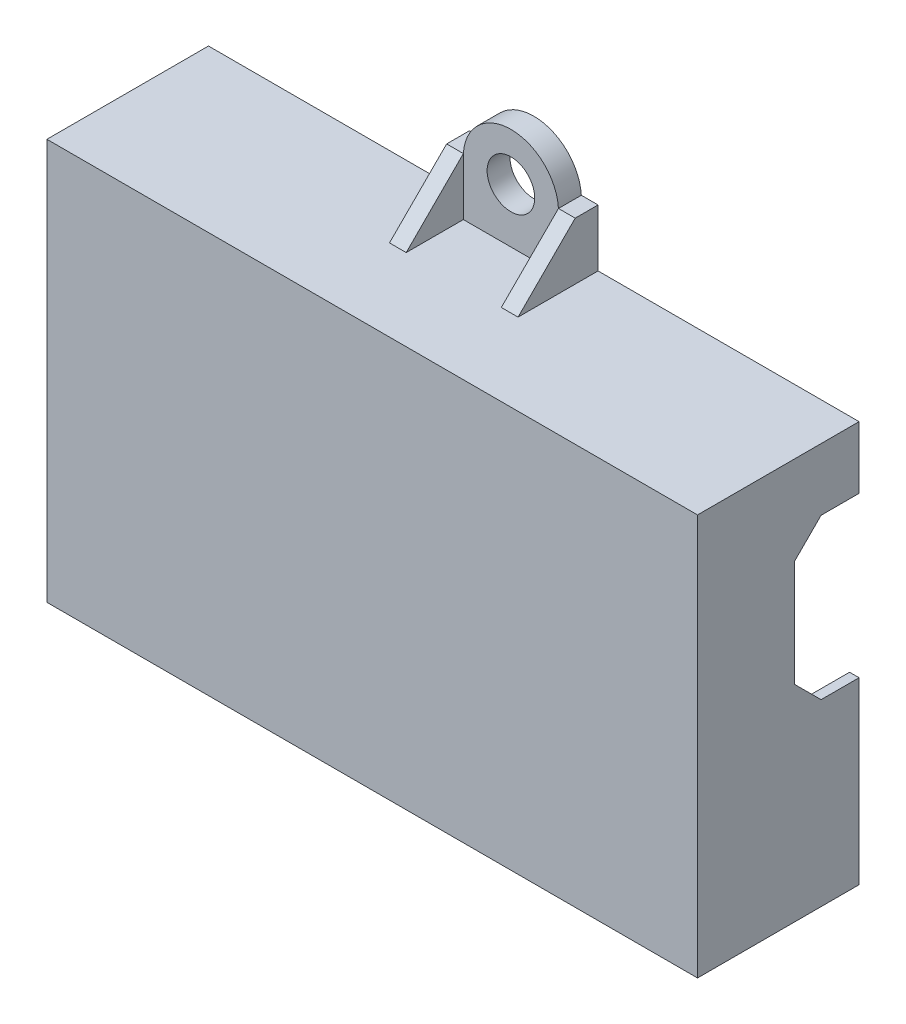
SolidWorks part; units mm, degrees
ref_plane "Front Plane" through (0, 0, 0) normal (0, 0, 1) x (1, 0, 0)
ref_plane "Top Plane" through (0, 0, 0) normal (0, 1, 0) x (1, 0, 0)
ref_plane "Right Plane" through (0, 0, 0) normal (1, 0, 0) x (0, 0, -1)
sketch "Sketch1" plane through (0, 0, 0) normal (0, 0, 1) x (1, 0, 0)
  line L0 (-16.375, 9.825) -> (16.375, -9.825) construction
  line L1 (-16.375, -9.825) -> (-16.575, -9.825) construction
  line L2 (16.575, 10.025) -> (-16.575, 10.025)
  line L3 (16.575, 10.025) -> (16.575, -10.025)
  line L4 (-16.375, 9.825) -> (-16.375, -9.825)
  line L5 (-16.375, -9.825) -> (16.375, -9.825)
  line L6 (16.375, -9.825) -> (16.375, 9.825)
  line L7 (16.375, 9.825) -> (-16.375, 9.825)
  line L8 (-16.375, 9.825) -> (-16.375, -9.825)
  line L9 (-16.375, -9.825) -> (16.375, -9.825)
  line L10 (16.375, -9.825) -> (16.375, 9.825)
  line L11 (16.375, 9.825) -> (-16.375, 9.825)
  line L12 (16.575, -10.025) -> (-16.575, -10.025)
  line L13 (-16.575, 10.025) -> (-16.575, -10.025)
  line L14 (16.575, 10.025) -> (-16.575, -10.025) construction
  line L15 (-13.9701, -11.875) -> (-3.4641, -11.875)
  line L18 (3.4641, -11.875) -> (13.9701, -11.875)
  line L19 (14.8161, -12.3418) -> (24.6724, -27.981)
  line L20 (31.4404, -23.7156) -> (19.404, -4.6171)
  line L21 (19.25, -4.084) -> (19.25, 4.084)
  line L22 (19.404, 4.6171) -> (31.4404, 23.7156)
  line L23 (24.6724, 27.981) -> (14.8161, 12.3418)
  line L24 (13.9701, 11.875) -> (3.4641, 11.875)
  line L25 (-3.4641, 11.875) -> (-13.9701, 11.875)
  line L26 (-14.8161, 12.3418) -> (-24.6724, 27.981)
  line L27 (-31.4404, 23.7156) -> (-19.404, 4.6171)
  line L28 (-19.25, 4.084) -> (-19.25, 3.4641)
  line L29 (-19.25, -3.4641) -> (-19.25, -4.084)
  line L30 (-19.404, -4.6171) -> (-31.4404, -23.7156)
  line L31 (-24.6724, -27.981) -> (-14.8161, -12.3418)
  line L32 (-13.9701, -11.875) -> (-3.4641, -11.875)
  line L33 (3.4641, -11.875) -> (13.9701, -11.875)
  line L34 (14.8161, -12.3418) -> (24.6724, -27.981)
  line L35 (31.4404, -23.7156) -> (19.404, -4.6171)
  line L36 (19.25, -4.084) -> (19.25, 4.084)
  line L37 (19.404, 4.6171) -> (31.4404, 23.7156)
  line L38 (24.6724, 27.981) -> (14.8161, 12.3418)
  line L39 (13.9701, 11.875) -> (3.4641, 11.875)
  line L40 (-3.4641, 11.875) -> (-13.9701, 11.875)
  line L41 (-14.8161, 12.3418) -> (-24.6724, 27.981)
  line L42 (-31.4404, 23.7156) -> (-19.404, 4.6171)
  line L43 (-19.25, 4.084) -> (-19.25, 3.4641)
  line L44 (-19.25, -3.4641) -> (-19.25, -4.084)
  line L45 (-19.404, -4.6171) -> (-31.4404, -23.7156)
  line L46 (-24.6724, -27.981) -> (-14.8161, -12.3418)
  line L47 (16.575, -10.025) -> (-16.575, 10.025) construction
  line L48 (-16.375, -9.825) -> (-16.375, -10.025) construction
  line L49 (-16.575, -10.025) -> (-17.075, -10.025) construction
  line L50 (17.075, 10.525) -> (-17.075, 10.525)
  line L51 (17.075, 10.525) -> (17.075, -10.525)
  line L52 (17.075, -10.525) -> (-17.075, -10.525)
  line L53 (-17.075, 10.525) -> (-17.075, -10.525)
  line L54 (17.075, 10.525) -> (-17.075, -10.525) construction
  line L55 (17.075, -10.525) -> (-17.075, 10.525) construction
  line L56 (-16.575, -10.025) -> (-16.575, -10.525) construction
  line L57 (-20.3929, -2.4744) -> (-17.075, -2.4744)
  line L58 (-20.3929, 2.4744) -> (-17.075, 2.4744)
  line L59 (-2.4744, -13.0179) -> (-2.4744, -10.525)
  line L60 (2.4744, -13.0179) -> (2.4744, -10.525)
  line L61 (-2.4744, 13.0179) -> (-2.4744, 10.525)
  line L62 (2.4744, 13.0179) -> (2.4744, 10.525)
  circle A0 centre (0, -13.375) radius 1.25
  circle A1 centre (-20.75, 0) radius 1.25
  circle A2 centre (0, 13.375) radius 1.25
  arc A32 (-2.4744, -13.0179) -> (-3.4641, -11.875) centre (-3.4641, -12.875) ccw
  arc A33 (-2.4744, -13.0179) -> (2.4744, -13.0179) centre (0, -13.375) ccw
  arc A34 (3.4641, -11.875) -> (2.4744, -13.0179) centre (3.4641, -12.875) ccw
  arc A35 (14.8161, -12.3418) -> (13.9701, -11.875) centre (13.9701, -12.875) ccw
  arc A36 (24.7505, -28.8963) -> (24.6724, -27.981) centre (23.8264, -28.5142) ccw
  arc A37 (24.7505, -28.8963) -> (32.2325, -24.1809) centre (31.8198, -31.8198) ccw
  arc A38 (31.4404, -23.7156) -> (32.2325, -24.1809) centre (32.2864, -23.1824) ccw
  arc A39 (19.25, -4.084) -> (19.404, -4.6171) centre (20.25, -4.084) ccw
  arc A40 (19.404, 4.6171) -> (19.25, 4.084) centre (20.25, 4.084) ccw
  arc A41 (32.2325, 24.1809) -> (31.4404, 23.7156) centre (32.2864, 23.1824) ccw
  arc A42 (32.2325, 24.1809) -> (24.7505, 28.8963) centre (31.8198, 31.8198) ccw
  arc A43 (24.6724, 27.981) -> (24.7505, 28.8963) centre (23.8264, 28.5142) ccw
  arc A44 (13.9701, 11.875) -> (14.8161, 12.3418) centre (13.9701, 12.875) ccw
  arc A45 (2.4744, 13.0179) -> (3.4641, 11.875) centre (3.4641, 12.875) ccw
  arc A46 (2.4744, 13.0179) -> (-2.4744, 13.0179) centre (0, 13.375) ccw
  arc A47 (-3.4641, 11.875) -> (-2.4744, 13.0179) centre (-3.4641, 12.875) ccw
  arc A48 (-14.8161, 12.3418) -> (-13.9701, 11.875) centre (-13.9701, 12.875) ccw
  arc A49 (-24.7505, 28.8963) -> (-24.6724, 27.981) centre (-23.8264, 28.5142) ccw
  arc A50 (-24.7505, 28.8963) -> (-32.2325, 24.1809) centre (-31.8198, 31.8198) ccw
  arc A51 (-31.4404, 23.7156) -> (-32.2325, 24.1809) centre (-32.2864, 23.1824) ccw
  arc A52 (-19.25, 4.084) -> (-19.404, 4.6171) centre (-20.25, 4.084) ccw
  arc A53 (-20.3929, 2.4744) -> (-19.25, 3.4641) centre (-20.25, 3.4641) ccw
  arc A54 (-20.3929, 2.4744) -> (-20.3929, -2.4744) centre (-20.75, 0) ccw
  arc A55 (-19.25, -3.4641) -> (-20.3929, -2.4744) centre (-20.25, -3.4641) ccw
  arc A56 (-19.404, -4.6171) -> (-19.25, -4.084) centre (-20.25, -4.084) ccw
  arc A57 (-32.2325, -24.1809) -> (-31.4404, -23.7156) centre (-32.2864, -23.1824) ccw
  arc A58 (-32.2325, -24.1809) -> (-24.7505, -28.8963) centre (-31.8198, -31.8198) ccw
  arc A59 (-24.6724, -27.981) -> (-24.7505, -28.8963) centre (-23.8264, -28.5142) ccw
  arc A60 (-13.9701, -11.875) -> (-14.8161, -12.3418) centre (-13.9701, -12.875) ccw
  arc A61 (-2.4744, -13.0179) -> (-3.4641, -11.875) centre (-3.4641, -12.875) ccw
  arc A62 (-2.4744, -13.0179) -> (2.4744, -13.0179) centre (0, -13.375) ccw
  arc A63 (3.4641, -11.875) -> (2.4744, -13.0179) centre (3.4641, -12.875) ccw
  arc A64 (14.8161, -12.3418) -> (13.9701, -11.875) centre (13.9701, -12.875) ccw
  arc A65 (24.7505, -28.8963) -> (24.6724, -27.981) centre (23.8264, -28.5142) ccw
  arc A66 (24.7505, -28.8963) -> (32.2325, -24.1809) centre (31.8198, -31.8198) ccw
  arc A67 (31.4404, -23.7156) -> (32.2325, -24.1809) centre (32.2864, -23.1824) ccw
  arc A68 (19.25, -4.084) -> (19.404, -4.6171) centre (20.25, -4.084) ccw
  arc A69 (19.404, 4.6171) -> (19.25, 4.084) centre (20.25, 4.084) ccw
  arc A70 (32.2325, 24.1809) -> (31.4404, 23.7156) centre (32.2864, 23.1824) ccw
  arc A71 (32.2325, 24.1809) -> (24.7505, 28.8963) centre (31.8198, 31.8198) ccw
  arc A72 (24.6724, 27.981) -> (24.7505, 28.8963) centre (23.8264, 28.5142) ccw
  arc A73 (13.9701, 11.875) -> (14.8161, 12.3418) centre (13.9701, 12.875) ccw
  arc A74 (2.4744, 13.0179) -> (3.4641, 11.875) centre (3.4641, 12.875) ccw
  arc A75 (2.4744, 13.0179) -> (-2.4744, 13.0179) centre (0, 13.375) ccw
  arc A76 (-3.4641, 11.875) -> (-2.4744, 13.0179) centre (-3.4641, 12.875) ccw
  arc A77 (-14.8161, 12.3418) -> (-13.9701, 11.875) centre (-13.9701, 12.875) ccw
  arc A78 (-24.7505, 28.8963) -> (-24.6724, 27.981) centre (-23.8264, 28.5142) ccw
  arc A79 (-24.7505, 28.8963) -> (-32.2325, 24.1809) centre (-31.8198, 31.8198) ccw
  arc A80 (-31.4404, 23.7156) -> (-32.2325, 24.1809) centre (-32.2864, 23.1824) ccw
  arc A81 (-19.25, 4.084) -> (-19.404, 4.6171) centre (-20.25, 4.084) ccw
  arc A82 (-20.3929, 2.4744) -> (-19.25, 3.4641) centre (-20.25, 3.4641) ccw
  arc A83 (-20.3929, 2.4744) -> (-20.3929, -2.4744) centre (-20.75, 0) ccw
  arc A84 (-19.25, -3.4641) -> (-20.3929, -2.4744) centre (-20.25, -3.4641) ccw
  arc A85 (-19.404, -4.6171) -> (-19.25, -4.084) centre (-20.25, -4.084) ccw
  arc A86 (-32.2325, -24.1809) -> (-31.4404, -23.7156) centre (-32.2864, -23.1824) ccw
  arc A87 (-32.2325, -24.1809) -> (-24.7505, -28.8963) centre (-31.8198, -31.8198) ccw
  arc A88 (-24.6724, -27.981) -> (-24.7505, -28.8963) centre (-23.8264, -28.5142) ccw
  arc A89 (-13.9701, -11.875) -> (-14.8161, -12.3418) centre (-13.9701, -12.875) ccw
  point P6 (0, 0)
  point P25 (0, 0)
  dimension "D4" = 0.5
  dimension "D5" = 2.5
  dimension "D1" = 0
  dimension "D2" = 0
  dimension "D3" = 0.2
extrude "Boss-Extrude1" add sketch "Sketch1" along normal offset from surface (7.98 mm away) 2.5 contours A84 L57 L53 L58 A82 A83 | L50 L53 L52 L51 L13 L2 L3 L12 | A63 L60 L52 L59 A61 A62 | A76 L61 L50 L62 A74 A75 region at (-2.4011, -11.6286, 0) region at (-9.7747, -10.1238, 0) region at (-18.5911, -2.3949, 0) region at (0, 10.5982, 0) offset beyond the face yes
sketch "Sketch2" plane through (0, 0, 7.98) normal (0, 0, 1) x (1, 0, 0)
  line L0 (-2.5, 10.525) -> (2.4744, 10.525)
  line L1 (-17.075, 2.5) -> (-17.075, -2.5)
  line L2 (-2.5, -10.525) -> (2.4744, -10.525)
  line L6 (-20.1071, -2.4744) -> (-17.075, -2.4744)
  line L7 (-20.1071, -2.4744) -> (-17.075, -2.4744)
  line L8 (-17.075, -2.4744) -> (-17.075, -10.525)
  line L9 (-17.075, -2.4744) -> (-17.075, -10.525)
  line L20 (-17.075, -10.525) -> (-2.4744, -10.525)
  line L21 (-17.075, -10.525) -> (-2.4744, -10.525)
  line L22 (-2.4744, -10.525) -> (-2.4744, -12.7321)
  line L23 (-2.4744, -10.525) -> (-2.4744, -12.7321)
  line L24 (2.4744, -12.7321) -> (2.4744, -10.525)
  line L25 (2.4744, -12.7321) -> (2.4744, -10.525)
  line L26 (2.4744, -10.525) -> (17.075, -10.525)
  line L27 (2.4744, -10.525) -> (17.075, -10.525)
  line L28 (17.075, -10.525) -> (17.075, 10.525)
  line L29 (17.075, -10.525) -> (17.075, 10.525)
  line L30 (17.075, 10.525) -> (2.4744, 10.525)
  line L31 (17.075, 10.525) -> (2.4744, 10.525)
  line L32 (2.4744, 10.525) -> (2.4744, 12.7321)
  line L33 (2.4744, 10.525) -> (2.4744, 12.7321)
  line L34 (-2.4744, 12.7321) -> (-2.4744, 10.525)
  line L35 (-2.4744, 12.7321) -> (-2.4744, 10.525)
  line L36 (-2.4744, 10.525) -> (-17.075, 10.525)
  line L37 (-2.4744, 10.525) -> (-17.075, 10.525)
  line L38 (-17.075, 10.525) -> (-17.075, 2.4744)
  line L39 (-17.075, 10.525) -> (-17.075, 2.4744)
  line L40 (-17.075, 2.4744) -> (-20.1071, 2.4744)
  line L41 (-17.075, 2.4744) -> (-20.1071, 2.4744)
  arc A9 (-20.1071, -2.4744) -> (-20.3929, -2.4744) centre (-20.25, -3.4641) ccw
  arc A10 (-20.1071, -2.4744) -> (-20.3929, -2.4744) centre (-20.25, -3.4641) ccw
  arc A11 (-2.4744, -13.0179) -> (-2.4744, -12.7321) centre (-3.4641, -12.875) ccw
  arc A12 (-2.4744, -13.0179) -> (-2.4744, -12.7321) centre (-3.4641, -12.875) ccw
  arc A13 (-2.4744, -13.0179) -> (2.4744, -13.0179) centre (0, -13.375) ccw
  arc A14 (-2.4744, -13.0179) -> (2.4744, -13.0179) centre (0, -13.375) ccw
  arc A15 (2.4744, -12.7321) -> (2.4744, -13.0179) centre (3.4641, -12.875) ccw
  arc A16 (2.4744, -12.7321) -> (2.4744, -13.0179) centre (3.4641, -12.875) ccw
  arc A17 (2.4744, 13.0179) -> (2.4744, 12.7321) centre (3.4641, 12.875) ccw
  arc A18 (2.4744, 13.0179) -> (2.4744, 12.7321) centre (3.4641, 12.875) ccw
  arc A19 (2.4744, 13.0179) -> (-2.4744, 13.0179) centre (0, 13.375) ccw
  arc A20 (2.4744, 13.0179) -> (-2.4744, 13.0179) centre (0, 13.375) ccw
  arc A21 (-2.4744, 12.7321) -> (-2.4744, 13.0179) centre (-3.4641, 12.875) ccw
  arc A22 (-2.4744, 12.7321) -> (-2.4744, 13.0179) centre (-3.4641, 12.875) ccw
  arc A23 (-20.3929, 2.4744) -> (-20.1071, 2.4744) centre (-20.25, 3.4641) ccw
  arc A24 (-20.3929, 2.4744) -> (-20.1071, 2.4744) centre (-20.25, 3.4641) ccw
  arc A25 (-20.3929, 2.4744) -> (-20.3929, -2.4744) centre (-20.75, 0) ccw
  arc A26 (-20.3929, 2.4744) -> (-20.3929, -2.4744) centre (-20.75, 0) ccw
  dimension "D1" = 0
extrude "Cut-Extrude1" cut sketch "Sketch2" against normal offset from surface (6.78 mm away) 1.2 contours L0 | L1 | L2 region at (0, 12.9704, 7.98) region at (-19.9289, 0, 7.98) region at (0, -12.9704, 7.98) up to face at (-5.364, 0, 0)
sketch "Sketch3" plane through (17.075, 0, 0) normal (1, 0, 0) x (0, 0, -1)
  line L0 (0, 10.525) -> (0, -10.525) construction
  line L1 (0, 7.265) -> (-3.395, 7.265)
  line L2 (0, 7.265) -> (0, -1.115)
  line L3 (0, -1.115) -> (-3.395, -1.115)
  line L4 (-3.395, 7.265) -> (-3.395, -1.115)
  line L6 (-1.3, 7.065) -> (-1.3, 7.265) construction
  line L7 (-1.3, -0.915) -> (-1.3, -1.115) construction
  line L8 (-3.195, 5.375) -> (-3.395, 5.375) construction
  dimension "D1" = 0.2
extrude "Cut-Extrude2" cut sketch "Sketch3" against normal up to next
chamfer "Chamfer1" distance 1.4 angle 45 2 edges at (16.825, -1.115, 3.395) (16.825, 7.265, 3.395)
sketch "Sketch4" plane through (0, 0, 7.98) normal (0, 0, 1) x (1, 0, 0)
  line L4 (-17.075, 10.525) -> (-17.075, -10.525)
  line L8 (-17.075, 10.525) -> (-17.075, -10.525)
  line L17 (-17.075, -10.525) -> (17.075, -10.525)
  line L18 (-17.075, -10.525) -> (17.075, -10.525)
  line L25 (17.075, -10.525) -> (17.075, 10.525)
  line L26 (17.075, -10.525) -> (17.075, 10.525)
  line L27 (17.075, 10.525) -> (-17.075, 10.525)
  line L28 (17.075, 10.525) -> (-17.075, 10.525)
  dimension "D1" = 0
extrude "Boss-Extrude2" add sketch "Sketch4" along normal blind 0.5
sketch "Sketch8" plane through (-17.075, 0, 0) normal (-1, 0, 0) x (0, 0, 1)
  line L1 (5.93, 3.385) -> (7.98, 3.385)
  line L2 (5.93, 3.385) -> (5.93, -3.385)
  line L3 (5.93, -3.385) -> (7.98, -3.385)
  line L4 (7.98, 3.385) -> (7.98, -3.385)
  line L7 (7.08, 3.385) -> (5.93, 3.385) construction
  line L8 (5.93, -3.385) -> (7.08, -3.385) construction
  line L9 (5.93, 3.385) -> (5.93, 2.4) construction
  line L10 (7.98, -3.985) -> (7.98, -2.4) construction
extrude "Cut-Extrude3" cut sketch "Sketch8" against normal up to next
sketch "Sketch9" plane through (0, 0, 7.98) normal (0, 0, -1) x (-1, 0, 0)
  line L1 (16.575, 2.4) -> (17.075, 2.4)
  line L2 (16.575, 2.4) -> (16.575, 3.385)
  line L3 (16.575, 3.385) -> (17.075, 3.385)
  line L4 (17.075, 2.4) -> (17.075, 3.385)
  line L5 (16.575, -2.4) -> (17.075, -2.4)
  line L6 (16.575, -2.4) -> (16.575, -3.385)
  line L7 (16.575, -3.385) -> (17.075, -3.385)
  line L8 (17.075, -2.4) -> (17.075, -3.385)
extrude "Boss-Extrude6" add sketch "Sketch9" along normal blind 0.8
sketch "Sketch11" plane through (0, 0, 7.98) normal (0, 0, -1) x (-1, 0, 0)
  line L24 (16.675, -4.085) -> (16.675, -2.3)
  line L25 (16.675, -2.3) -> (15.385, -2.3)
  line L26 (15.385, -2.3) -> (15.385, 2.3)
  line L27 (15.385, 2.3) -> (16.675, 2.3)
  line L28 (16.675, 2.3) -> (16.675, 4.085)
  line L29 (16.675, 4.085) -> (10.255, 4.085)
  line L30 (10.255, 4.085) -> (10.255, 2.4)
  line L31 (10.255, 2.4) -> (5.655, 2.4)
  line L32 (5.655, 2.4) -> (5.655, -2.4)
  line L33 (5.655, -2.4) -> (10.255, -2.4)
  line L34 (10.255, -2.4) -> (10.255, -4.085)
  line L35 (10.255, -4.085) -> (16.675, -4.085)
  line L36 (16.675, -4.085) -> (16.675, -2.3)
  line L37 (16.675, -2.3) -> (15.385, -2.3)
  line L38 (15.385, -2.3) -> (15.385, 2.3)
  line L39 (15.385, 2.3) -> (16.675, 2.3)
  line L40 (16.675, 2.3) -> (16.675, 4.085)
  line L41 (16.675, 4.085) -> (10.255, 4.085)
  line L42 (10.255, 4.085) -> (10.255, 2.4)
  line L43 (10.255, 2.4) -> (5.655, 2.4)
  line L44 (5.655, 2.4) -> (5.655, -2.4)
  line L45 (5.655, -2.4) -> (10.255, -2.4)
  line L46 (10.255, -2.4) -> (10.255, -4.085)
  line L47 (10.255, -4.085) -> (16.675, -4.085)
  line L48 (5.655, 1.9) -> (3.655, 1.9)
  line L49 (3.655, 0) -> (17.385, 0) construction
  line L50 (5.655, -1.9) -> (3.655, -1.9)
  line L51 (16.575, 6.085) -> (16.575, 4.085)
  line L53 (16.575, 10.025) -> (16.575, 2.4) construction
  line L54 (16.575, -6.085) -> (16.575, -4.085)
  line L55 (16.575, -2.4) -> (16.575, -10.025) construction
  line L60 (18.675, -6.085) -> (18.675, -0.3)
  line L61 (18.675, -0.3) -> (17.385, -0.3)
  line L62 (17.385, -0.3) -> (17.385, 0.3)
  line L63 (17.385, 0.3) -> (18.675, 0.3)
  line L64 (18.675, 0.3) -> (18.675, 6.085)
  line L65 (18.675, 6.085) -> (8.255, 6.085)
  line L66 (8.255, 6.085) -> (8.255, 4.4)
  line L67 (8.255, 4.4) -> (3.655, 4.4)
  line L68 (3.655, 4.4) -> (3.655, -4.4)
  line L69 (3.655, -4.4) -> (8.255, -4.4)
  line L70 (8.255, -4.4) -> (8.255, -6.085)
  line L71 (8.255, -6.085) -> (18.675, -6.085)
  line L72 (18.675, -6.085) -> (18.675, -0.3)
  line L73 (18.675, -0.3) -> (17.385, -0.3)
  line L74 (17.385, -0.3) -> (17.385, 0.3)
  line L75 (17.385, 0.3) -> (18.675, 0.3)
  line L76 (18.675, 0.3) -> (18.675, 6.085)
  line L77 (18.675, 6.085) -> (8.255, 6.085)
  line L78 (8.255, 6.085) -> (8.255, 4.4)
  line L79 (8.255, 4.4) -> (3.655, 4.4)
  line L80 (3.655, 4.4) -> (3.655, -4.4)
  line L81 (3.655, -4.4) -> (8.255, -4.4)
  line L82 (8.255, -4.4) -> (8.255, -6.085)
  line L83 (8.255, -6.085) -> (18.675, -6.085)
  line M27 (16.575, -10.025) -> (16.575, -2.4)
  line M31 (16.575, 2.4) -> (16.575, 10.025)
  dimension "D3" = 0.5
  dimension "D1" = 0.1
  dimension "D2" = 2.1
extrude "Boss-Extrude7" add sketch "Sketch11" along normal blind 2.5 contours L79 L80 L48 L44 L43 L42 L41 L77 L78 M31 | L82 L83 L47 L46 L45 L44 L50 L80 L81 M27 region at (-9.8383, -4.2692, 7.98) region at (-9.8383, 4.2692, 7.98)
sketch "Sketch12" plane through (0, 0, 7.98) normal (0, 0, -1) x (-1, 0, 0)
  line L0 (16.575, -6.085) -> (16.575, -10.025) construction
  line L1 (-3.0335, 0) -> (1.6631, 0) construction
  line L2 (16.575, 8.055) -> (14.605, 8.055)
  line L3 (16.575, 8.055) -> (16.575, 6.085)
  line L4 (16.575, 6.085) -> (14.605, 6.085)
  line L5 (16.575, -8.055) -> (14.605, -8.055)
  line L6 (16.575, -8.055) -> (16.575, -6.085)
  line L7 (16.575, -6.085) -> (14.605, -6.085)
  line L8 (14.605, -8.055) -> (14.605, -6.085)
  line L9 (8.255, -6.085) -> (16.575, -6.085) construction
  line L10 (14.605, 8.055) -> (14.605, 6.085)
  line L11 (-16.575, 10.025) -> (-16.575, -10.025) construction
  line L12 (-14.605, 2) -> (-16.575, 2)
  line L13 (-14.605, 2) -> (-14.605, -2)
  line L14 (-14.605, -2) -> (-16.575, -2)
  line L15 (-16.575, 2) -> (-16.575, -2)
  line L16 (-14.605, 2) -> (-16.575, -2) construction
  line L17 (-14.605, -2) -> (-16.575, 2) construction
  point P16 (-15.59, 0)
  dimension "D1" = 4
extrude "Boss-Extrude8" add sketch "Sketch12" along normal up to surface (3.95 mm away)
sketch "Sketch13" plane through (-17.075, 0, 0) normal (-1, 0, 0) x (0, 0, 1)
  line L0 (7.18, 2.4) -> (7.18, 3.385) construction
  line L1 (7.98, 2.4) -> (7.18, 2.4)
  line L2 (7.98, 2.4) -> (7.98, 2.9)
  line L3 (7.98, 2.9) -> (7.18, 2.9)
  line L4 (7.18, 2.4) -> (7.18, 2.9)
  line L5 (5.93, 0) -> (7.98, 0) construction
  line L6 (7.18, 3.385) -> (5.43, 3.385)
  line L7 (7.18, 3.385) -> (7.18, 3.885)
  line L8 (7.18, 3.885) -> (5.43, 3.885)
  line L9 (5.43, 3.385) -> (5.43, 3.885)
  line L10 (5.93, 3.385) -> (5.93, -3.385) construction
  line L11 (7.98, -2) -> (7.98, 2) construction
  line L12 (5.43, 1.6925) -> (5.93, 1.6925) construction
  line L13 (5.43, 3.385) -> (5.93, 3.385)
  line L14 (5.43, 3.385) -> (5.43, -3.385)
  line L15 (5.93, 0) -> (5.93, -3.385)
  line L16 (5.93, 3.385) -> (5.93, 0)
  line L17 (7.98, -2.4) -> (7.98, -2.9)
  line L18 (7.98, -2.9) -> (7.18, -2.9)
  line L19 (7.18, -3.385) -> (7.18, -3.885)
  line L20 (7.18, -3.885) -> (5.43, -3.885)
  line L21 (5.43, -3.385) -> (5.43, -3.885)
  line L22 (5.43, 3.385) -> (5.43, -3.385)
  line L23 (1.2, -2.5) -> (1.2, 2.5) construction
  line L24 (0, 3.3744) -> (1.2, 3.3744)
  line L25 (0, 3.3744) -> (0, 5.8744)
  line L26 (0, 5.8744) -> (1.2, 5.8744)
  line L27 (1.2, 3.3744) -> (1.2, 5.8744)
  line L28 (1.2, 2.4744) -> (0, 2.4744) construction
  line L29 (0, 10.525) -> (0, 2.4744) construction
  point P37 (0, 0)
  point P38 (0, 0)
  line M12 (7.98, -2.4) -> (7.18, -2.4)
  line M13 (7.18, -2.4) -> (7.18, -3.385)
  line M14 (7.18, -3.385) -> (5.93, -3.385)
  line M15 (5.93, -3.385) -> (5.93, 3.385)
  line M16 (5.93, 3.385) -> (7.18, 3.385)
  line M17 (7.18, 3.385) -> (7.18, 2.4)
  line M18 (7.18, 2.4) -> (7.98, 2.4)
  line M22 (0, 10.525) -> (0, 2.4744)
  dimension "D1" = 0.5
  dimension "D2" = 2.5
  dimension "D3" = 0.9
extrude "Cut-Extrude4" cut sketch "Sketch13" against normal up to next contours L9 L6 L7 L8 M16 | L2 L3 M17 M18 | L14 L21 L20 L19 L6 M14 M15 | L18 L17 M12 M13 | L24 L27 L26 M22 region at (-17.075, -2.65, 7.58) region at (-17.075, 3.635, 6.305) region at (-17.075, 2.65, 7.58) region at (-17.075, -0.7466, 5.8084) region at (-17.075, 4.6244, 0.6)
sketch "Sketch14" plane through (0, 0, 5.48) normal (0, 0, -1) x (-1, 0, 0)
  line L0 (16.575, 4.085) -> (10.255, 4.085) construction
  line L1 (16.575, 6.085) -> (14.175, 6.085)
  line L2 (16.575, 6.085) -> (16.575, 3.685)
  line L3 (16.575, 3.685) -> (14.175, 3.685)
  line L4 (14.175, 6.085) -> (14.175, 3.685)
  line L5 (3.655, 1.9) -> (3.655, -1.9) construction
  line L6 (3.655, 0) -> (16.575, 0) construction
  line L8 (16.575, -6.085) -> (16.575, -3.685)
  line L9 (16.575, -6.085) -> (14.175, -6.085)
  line L10 (14.175, -6.085) -> (14.175, -3.685)
  line L11 (16.575, -3.685) -> (14.175, -3.685)
  line L12 (5.655, 2.4) -> (5.655, 1.9) construction
  line L13 (3.655, 4.4) -> (5.655, 4.4)
  line L14 (3.655, 4.4) -> (3.655, 1.5)
  line L15 (3.655, 1.5) -> (5.655, 1.5)
  line L16 (5.655, 4.4) -> (5.655, 1.5)
  line L17 (15.375, 3.685) -> (15.375, 4.085) construction
  line L18 (16.575, 4.085) -> (10.255, 4.085) construction
  line L19 (4.655, 1.5) -> (4.655, 1.9) construction
  line L20 (5.655, 1.9) -> (3.655, 1.9) construction
  line L21 (3.655, -4.4) -> (5.655, -4.4)
  line L22 (5.655, -4.4) -> (5.655, -1.5)
  line L23 (3.655, -1.5) -> (5.655, -1.5)
  line L24 (3.655, -4.4) -> (3.655, -1.5)
  line L25 (16.575, 3.3744) -> (16.575, -10.025) construction
  dimension "D1" = 0.4
extrude "Boss-Extrude9" add sketch "Sketch14" along normal blind 0.6
ref_plane "Plane1" through (0, 0, 2.95) normal (0, 0, -1) x (-1, 0, 0)
sketch "Sketch16" plane through (0, 0, 2.95) normal (0, 0, -1) x (-1, 0, 0)
  line L0 (-16.575, 10.025) -> (16.575, 10.025) construction
  line L1 (6.075, 10.025) -> (8.575, 10.025)
  line L2 (6.075, 10.025) -> (6.075, 9.325)
  line L3 (6.075, 9.325) -> (8.575, 9.325)
  line L4 (8.575, 10.025) -> (8.575, 9.325)
  line L6 (16.575, 10.025) -> (16.575, 5.8744) construction
  line L8 (-16.575, 10.025) -> (-14.075, 10.025)
  line L9 (-16.575, 10.025) -> (-16.575, 9.325)
  line L10 (-16.575, 9.325) -> (-14.075, 9.325)
  line L11 (-14.075, 10.025) -> (-14.075, 9.325)
  line L12 (16.575, -10.025) -> (14.075, -10.025)
  line L13 (16.575, -10.025) -> (16.575, -9.325)
  line L14 (16.575, -9.325) -> (14.075, -9.325)
  line L15 (14.075, -10.025) -> (14.075, -9.325)
  line L16 (-16.575, -10.025) -> (-14.075, -10.025)
  line L17 (-16.575, -10.025) -> (-16.575, -9.325)
  line L18 (-16.575, -9.325) -> (-14.075, -9.325)
  line L19 (-14.075, -10.025) -> (-14.075, -9.325)
  dimension "D1" = 2.5
  dimension "D2" = 0.7
  dimension "D3" = 8
extrude "Boss-Extrude13" add sketch "Sketch16" along normal blind 0.8
chamfer "Chamfer2" distance 1 angle 45 2 edges at (-10.255, 3.2425, 5.48) (-10.255, -3.2425, 5.48)
sketch "Sketch17" plane through (0, 0, 1.2) normal (0, 0, 1) x (1, 0, 0)
  line L0 (-23.25, 0) -> (-17.075, 0) construction
  line L1 (-17.075, 10.525) -> (-17.075, -10.525) construction
  line L2 (0, 15.875) -> (0, -15.875) construction
  line L3 (-20.1071, 2.4744) -> (-17.075, 2.4744) construction
  line L4 (-20.075, -3.3744) -> (-17.075, -3.3744)
  line L5 (-20.075, -3.3744) -> (-20.075, 3.3744)
  line L6 (-20.075, 3.3744) -> (-17.075, 3.3744)
  line L7 (-17.075, -3.3744) -> (-17.075, 3.3744)
  line L8 (-20.075, -3.3744) -> (-17.075, 3.3744) construction
  line L9 (-20.075, 3.3744) -> (-17.075, -3.3744) construction
  line L10 (17.075, 10.525) -> (-17.075, 10.525) construction
  line L11 (-3.3744, 10.525) -> (3.3744, 10.525)
  line L12 (-3.3744, 10.525) -> (-3.3744, 13.525)
  line L13 (-20.1071, -2.4744) -> (-17.075, -2.4744)
  line L14 (-17.075, -2.4744) -> (-17.075, 2.4744)
  line L15 (-17.075, 2.4744) -> (-20.1071, 2.4744)
  line L16 (-20.1071, -2.4744) -> (-17.075, -2.4744)
  line L17 (-17.075, -2.4744) -> (-17.075, 2.4744)
  line L18 (-17.075, 2.4744) -> (-20.1071, 2.4744)
  line L19 (-2.4744, 12.7321) -> (-2.4744, 10.525)
  line L20 (-2.4744, 10.525) -> (2.4744, 10.525)
  line L21 (2.4744, 10.525) -> (2.4744, 12.7321)
  line L22 (-2.4744, 12.7321) -> (-2.4744, 10.525)
  line L23 (-2.4744, 10.525) -> (2.4744, 10.525)
  line L24 (2.4744, 10.525) -> (2.4744, 12.7321)
  line L25 (2.4744, -12.7321) -> (2.4744, -10.525)
  line L26 (2.4744, -10.525) -> (-2.4744, -10.525)
  line L27 (-2.4744, -10.525) -> (-2.4744, -12.7321)
  line L28 (2.4744, -12.7321) -> (2.4744, -10.525)
  line L29 (2.4744, -10.525) -> (-2.4744, -10.525)
  line L30 (-2.4744, -10.525) -> (-2.4744, -12.7321)
  line L31 (-3.3744, 13.525) -> (3.3744, 13.525)
  line L32 (3.3744, 10.525) -> (3.3744, 13.525)
  line L33 (-3.3744, 10.525) -> (3.3744, 13.525) construction
  line L34 (-3.3744, 13.525) -> (3.3744, 10.525) construction
  line L35 (-17.075, -10.525) -> (17.075, -10.525) construction
  line L36 (3.3744, -13.525) -> (-3.3744, -13.525)
  line L37 (3.3744, -13.525) -> (3.3744, -10.525)
  line L38 (3.3744, -10.525) -> (-3.3744, -10.525)
  line L39 (-3.3744, -13.525) -> (-3.3744, -10.525)
  line L40 (3.3744, -13.525) -> (-3.3744, -10.525) construction
  line L41 (3.3744, -10.525) -> (-3.3744, -13.525) construction
  arc A0 (-20.3929, 2.4744) -> (-20.3929, -2.4744) centre (-20.75, 0) ccw construction
  arc A1 (2.4744, 13.0179) -> (-2.4744, 13.0179) centre (0, 13.375) ccw construction
  arc A2 (-2.4744, -13.0179) -> (2.4744, -13.0179) centre (0, -13.375) ccw construction
  arc A6 (-20.3929, 2.4744) -> (-20.1071, 2.4744) centre (-20.25, 3.4641) ccw
  arc A7 (-20.3929, 2.4744) -> (-20.3929, -2.4744) centre (-20.75, 0) ccw
  arc A8 (-20.1071, -2.4744) -> (-20.3929, -2.4744) centre (-20.25, -3.4641) ccw
  arc A9 (-20.3929, 2.4744) -> (-20.1071, 2.4744) centre (-20.25, 3.4641) ccw
  arc A10 (-20.3929, 2.4744) -> (-20.3929, -2.4744) centre (-20.75, 0) ccw
  arc A11 (-20.1071, -2.4744) -> (-20.3929, -2.4744) centre (-20.25, -3.4641) ccw
  arc A12 (2.4744, 13.0179) -> (2.4744, 12.7321) centre (3.4641, 12.875) ccw
  arc A13 (2.4744, 13.0179) -> (-2.4744, 13.0179) centre (0, 13.375) ccw
  arc A14 (-2.4744, 12.7321) -> (-2.4744, 13.0179) centre (-3.4641, 12.875) ccw
  arc A15 (2.4744, 13.0179) -> (2.4744, 12.7321) centre (3.4641, 12.875) ccw
  arc A16 (2.4744, 13.0179) -> (-2.4744, 13.0179) centre (0, 13.375) ccw
  arc A17 (-2.4744, 12.7321) -> (-2.4744, 13.0179) centre (-3.4641, 12.875) ccw
  arc A18 (-2.4744, -13.0179) -> (-2.4744, -12.7321) centre (-3.4641, -12.875) ccw
  arc A19 (-2.4744, -13.0179) -> (2.4744, -13.0179) centre (0, -13.375) ccw
  arc A20 (2.4744, -12.7321) -> (2.4744, -13.0179) centre (3.4641, -12.875) ccw
  arc A21 (-2.4744, -13.0179) -> (-2.4744, -12.7321) centre (-3.4641, -12.875) ccw
  arc A22 (-2.4744, -13.0179) -> (2.4744, -13.0179) centre (0, -13.375) ccw
  arc A23 (2.4744, -12.7321) -> (2.4744, -13.0179) centre (3.4641, -12.875) ccw
  point P15 (-18.575, 0)
  point P38 (0, 12.025)
  point P57 (0, -12.025)
  line M26 (2.4744, -12.7321) -> (2.4744, -10.525)
  line M28 (-2.4744, -10.525) -> (-2.4744, -12.7321)
  arc M29 (-2.4744, -12.7321) -> (-2.4744, -13.0179) centre (-3.4641, -12.875) cw
  arc M30 (-2.4744, -13.0179) -> (2.4744, -13.0179) centre (0, -13.375) ccw
  arc M31 (2.4744, -13.0179) -> (2.4744, -12.7321) centre (3.4641, -12.875) cw
  dimension "D1" = 0.9
  dimension "D2" = 3
  dimension "D3" = 0
  dimension "D4" = 0
  dimension "D5" = 0
extrude "Boss-Extrude17" add sketch "Sketch17" against normal up to surface (1.2 mm away) contours L18 L7 L6 L5 | L16 L5 L4 L7 | L22 A17 A16 L31 L12 L11 | A16 A15 L24 L11 L32 L31 | L37 L38 L36 M26 M31 M30 | L39 L36 L38 M30 M29 M28 region at (-18.575, -2.9244, 1.2) region at (-18.575, 2.9244, 1.2) region at (-2.9256, 12.0209, 1.2) region at (2.9256, 12.0209, 1.2) region at (2.9256, -12.0209, 1.2) region at (-2.9256, -12.0209, 1.2) up to face at (-5.9004, -5.5994, 0)
sketch "Sketch18" plane through (0, 0, 1.2) normal (0, 0, 1) x (1, 0, 0)
  line L0 (-17.075, -3.3744) -> (-17.075, 3.3744) construction
  line L1 (-20.075, 3.3744) -> (-17.075, 3.3744)
  line L2 (-20.075, 3.3744) -> (-20.075, 2.4744)
  line L3 (-20.075, 2.4744) -> (-17.075, 2.4744)
  line L4 (-17.075, 3.3744) -> (-17.075, 2.4744)
  line L5 (-17.075, 10.525) -> (-17.075, -10.525) construction
  line L6 (-20.075, -2.4744) -> (-17.075, -2.4744)
  line L7 (-20.075, -2.4744) -> (-20.075, -3.3744)
  line L8 (-20.075, -3.3744) -> (-17.075, -3.3744)
  line L9 (-17.075, -2.4744) -> (-17.075, -3.3744)
  line L10 (17.075, 10.525) -> (-17.075, 10.525) construction
  line L11 (-2.4955, -13.525) -> (-3.3744, -13.525)
  line L12 (-2.4955, -13.525) -> (-2.4955, -10.525)
  line L13 (-2.4955, -10.525) -> (-3.3744, -10.525)
  line L14 (-3.3744, -13.525) -> (-3.3744, -10.525)
  line L15 (2.4955, -13.525) -> (3.3744, -13.525)
  line L16 (2.4955, -13.525) -> (2.4955, -10.525)
  line L17 (2.4955, -10.525) -> (3.3744, -10.525)
  line L18 (3.3744, -13.525) -> (3.3744, -10.525)
  line L19 (-2.4955, 13.525) -> (-3.3744, 13.525)
  line L20 (-2.4955, 13.525) -> (-2.4955, 10.525)
  line L21 (-2.4955, 10.525) -> (-3.3744, 10.525)
  line L22 (-3.3744, 13.525) -> (-3.3744, 10.525)
  line L23 (-3.3744, 10.525) -> (-3.3744, 13.525) construction
  line L25 (2.4955, 13.525) -> (3.3744, 13.525)
  line L26 (2.4955, 13.525) -> (2.4955, 10.525)
  line L27 (2.4955, 10.525) -> (3.3744, 10.525)
  line L28 (3.3744, 13.525) -> (3.3744, 10.525)
extrude "Boss-Extrude18" add sketch "Sketch18" along normal blind 3
chamfer "Chamfer3" distance 3 angle 45 6 edges at (-2.9349, 13.525, 4.2) (2.9349, 13.525, 4.2) (2.9349, -13.525, 4.2) (-2.9349, -13.525, 4.2) (-20.075, -2.9244, 4.2) (-20.075, 2.9244, 4.2)
